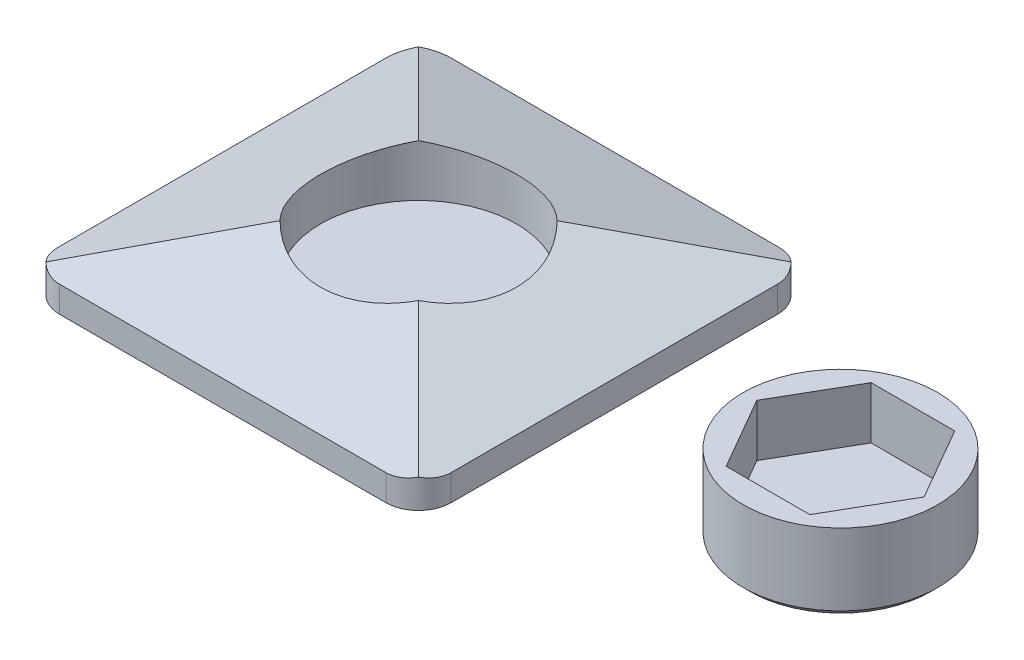
SolidWorks part; units mm, degrees
ref_plane "Alzado" through (0, 0, 0) normal (0, 0, 1) x (1, 0, 0)
ref_plane "Planta" through (0, 0, 0) normal (0, 1, 0) x (1, 0, 0)
ref_plane "Vista lateral" through (0, 0, 0) normal (1, 0, 0) x (0, 0, -1)
sketch "Croquis1" plane through (0, 0, 0) normal (0, 1, 0) x (1, 0, 0)
  line L1 (-30, 30) -> (30, 30)
  line L2 (-30, 30) -> (-30, -30)
  line L3 (-30, -30) -> (30, -30)
  line L4 (30, 30) -> (30, -30)
  line L5 (-30, 30) -> (30, -30) construction
  line L6 (-30, -30) -> (30, 30) construction
  point P0 (0, 0)
  dimension "D1" = 60
extrude "Saliente-Extruir1" add sketch "Croquis1" along normal blind 10
sketch "Croquis2" plane through (0, 10, 0) normal (0, 1, 0) x (1, 0, 0)
  circle A0 centre (0, 0) radius 15
  dimension "D1" = 30
extrude "Cortar-Extruir1" cut sketch "Croquis2" against normal blind 8
sketch "Croquis3" plane through (0, 0, 0) normal (0, -1, 0) x (1, 0, 0)
  circle A0 centre (64.6418, 0) radius 14.9
  dimension "D1" = 29.8
extrude "Saliente-Extruir2" add sketch "Croquis3" against normal blind 12 separate body
sketch "Croquis4" plane through (0, 12, 0) normal (0, 1, 0) x (1, 0, 0)
  line L1 (77.459, 0) -> (71.0504, 11.1)
  line L2 (71.0504, 11.1) -> (58.2332, 11.1)
  line L3 (58.2332, 11.1) -> (51.8247, 0)
  line L4 (51.8247, 0) -> (58.2332, -11.1)
  line L5 (58.2332, -11.1) -> (71.0504, -11.1)
  line L6 (71.0504, -11.1) -> (77.459, 0)
  circle A0 centre (64.6418, 0) radius 11.1 construction
  dimension "D1" = 22.2
extrude "Cortar-Extruir2" cut sketch "Croquis4" against normal blind 8
chamfer "Chaflán1" distance 1 angle 45 1 edges at (64.6418, 0, -14.9)
chamfer "Chaflán2" distance 6 angle 73 4 edges at (0, 10, -30) (-30, 10, 0) (0, 10, 30) (30, 10, 0) first distance on face at (0, 5, -30) first distance on face at (-30, 5, 0) first distance on face at (0, 5, 30) first distance on face at (30, 5, 0)
fillet "Redondeo1" radius 5 4 edges at (-30, 2, -30) (-30, 2, 30) (30, 2, -30) (30, 2, 30)
